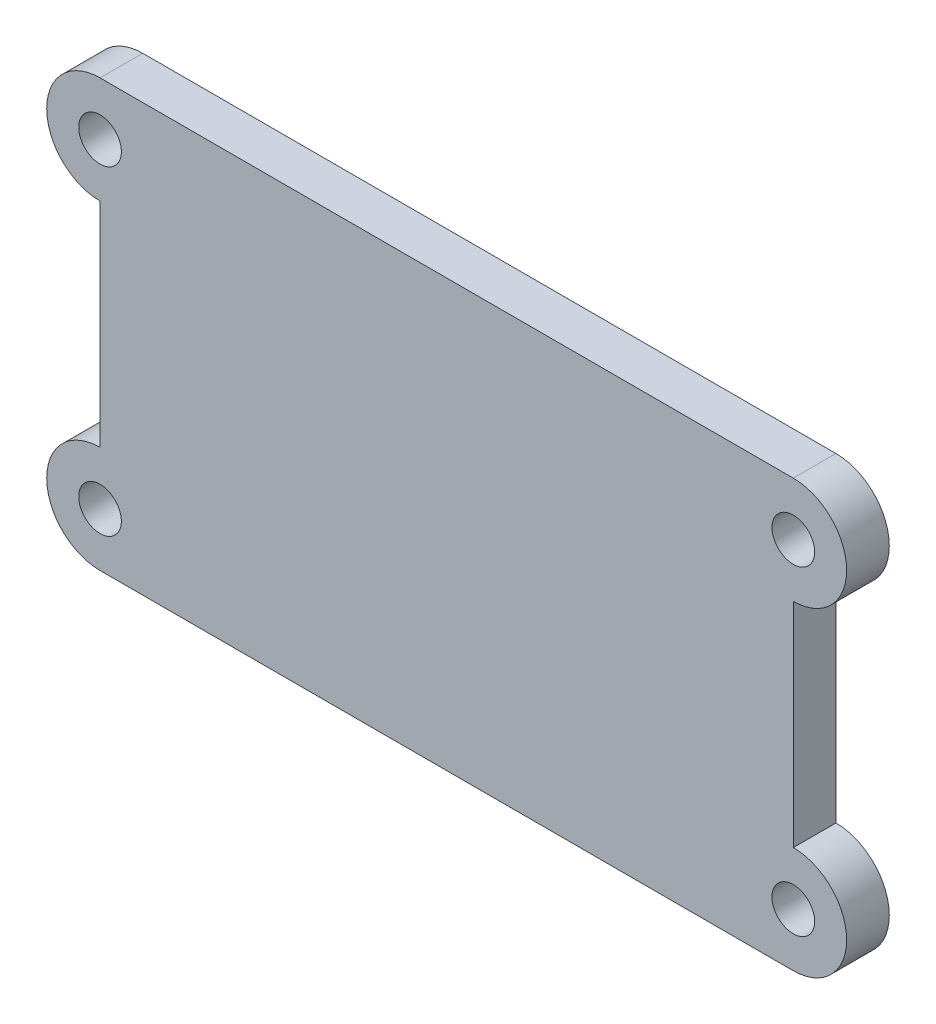
SolidWorks part; units mm, degrees
ref_plane "Front Plane" through (0, 0, 0) normal (0, 0, 1) x (1, 0, 0)
ref_plane "Top Plane" through (0, 0, 0) normal (0, 1, 0) x (1, 0, 0)
ref_plane "Right Plane" through (0, 0, 0) normal (1, 0, 0) x (0, 0, -1)
sketch "Sketch1" plane through (0, 0, 0) normal (0, 0, 1) x (1, 0, 0)
  line L1 (-32.5, 20) -> (32.5, 20)
  line L2 (-32.5, 20) -> (-32.5, -20)
  line L3 (-32.5, -20) -> (32.5, -20)
  line L4 (32.5, 20) -> (32.5, -20)
  line L5 (-32.5, 20) -> (32.5, -20) construction
  line L6 (-32.5, -20) -> (32.5, 20) construction
  point P0 (0, 0)
  dimension "D1" = 40
  dimension "D2" = 65
extrude "Boss-Extrude1" add sketch "Sketch1" along normal blind 4
sketch "Sketch2" plane through (0, 0, 0) normal (0, 0, 1) x (1, 0, 0)
  line L0 (-32.5, 20) -> (-32.5, -20) construction
  line L1 (-32.5, 20) -> (-32.5, 10)
  arc A0 (-32.5, 20) -> (-32.5, 10) centre (-32.5, 15) ccw
  dimension "D1" = 10
extrude "Boss-Extrude2" add sketch "Sketch2" along normal blind 4
sketch "Sketch3" plane through (0, 0, 4) normal (0, 0, 1) x (1, 0, 0)
  circle A0 centre (-32.5, 15) radius 2
  dimension "D1" = 4
extrude "Cut-Extrude1" cut sketch "Sketch3" against normal blind 4
mirror "Mirror1" about plane through (0, 0, 0) normal (0, 1, 0) of "Boss-Extrude2", "Cut-Extrude1" second plane through (0, 0, 0) second plane normal (1, 0, 0)
